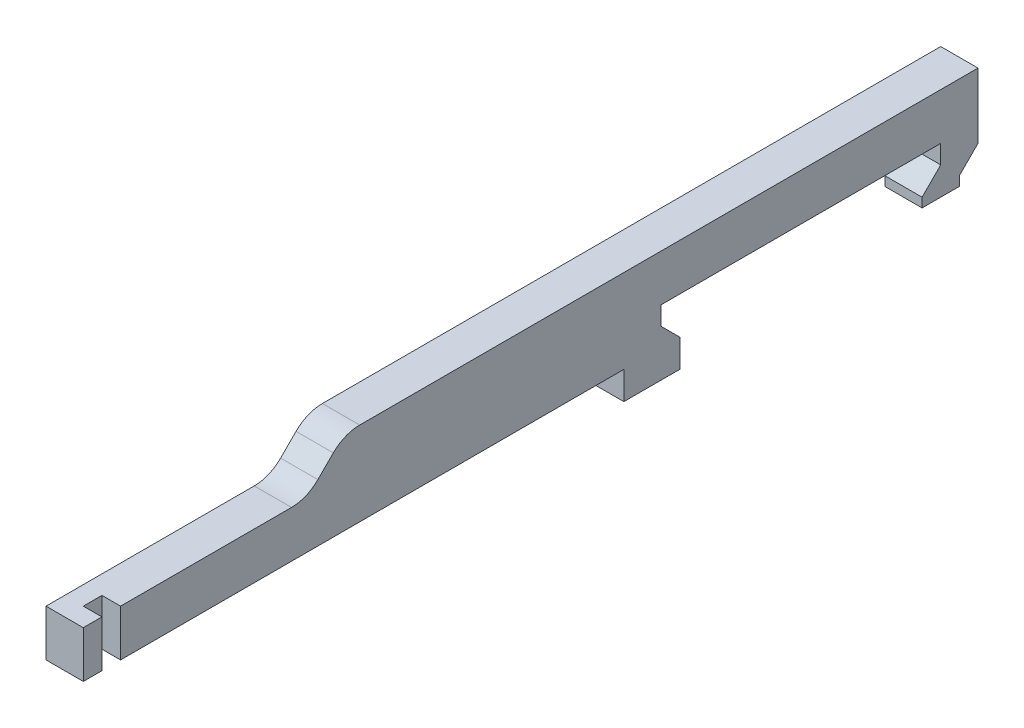
SolidWorks part; units mm, degrees
ref_plane "Спереди" through (0, 0, 0) normal (0, 0, 1) x (1, 0, 0)
ref_plane "Сверху" through (0, 0, 0) normal (0, 1, 0) x (1, 0, 0)
ref_plane "Справа" through (0, 0, 0) normal (1, 0, 0) x (0, 0, -1)
sketch "Эскиз1" plane through (0, 0, 0) normal (1, 0, 0) x (0, 0, -1)
  line L0 (12, 2.5) -> (14, 4.5)
  line L1 (0, 0) -> (12, 0)
  line L2 (0, 0) -> (0, 2.5)
  line L3 (0, 2.5) -> (12, 2.5)
  line L4 (12, 0) -> (12, 2.5)
  line L5 (14, 4.5) -> (14, 2.5) construction
  line L6 (14, 2.5) -> (12, 2.5) construction
  line L7 (14, 4.5) -> (29, 4.5)
  line L8 (12, 0) -> (29, 0)
  line L9 (29, 0) -> (29, -1.5)
  line L10 (29, -1.5) -> (32, -1.5)
  line L11 (32, -1.5) -> (32, 0)
  line L12 (32, 0) -> (31, 1)
  line L13 (31, 1) -> (31, 2)
  line L14 (31, 2) -> (46, 2)
  line L15 (32, 0) -> (31, 0) construction
  line L16 (31, 0) -> (31, 1) construction
  line L17 (38.5, 2) -> (38.5, 1) construction
  line L18 (45, 0) -> (46, 1)
  line L19 (46, 1) -> (46, 2)
  line L20 (45, 0) -> (45, -0.5)
  line L21 (45, -0.5) -> (47, -0.5)
  line L22 (47, -0.5) -> (47, 0)
  line L23 (47, 0) -> (48, 1)
  line L24 (48, 1) -> (48, 4.5)
  line L25 (48, 4.5) -> (29, 4.5)
  dimension "D1" = 2.5
  dimension "D2" = 12
  dimension "D3" = 2
  dimension "D4" = 2
  dimension "D5" = 15
  dimension "D6" = 17
  dimension "D7" = 1.5
  dimension "D8" = 3
  dimension "D9" = 1.5
  dimension "D10" = 1
  dimension "D11" = 1
  dimension "D12" = 1
  dimension "D13" = 15
  dimension "D14" = 0.5
  dimension "D15" = 2
extrude "Бобышка-Вытянуть1" add sketch "Эскиз1" along normal blind 2 contours L24 L25 L7 L0 L4 L8 L9 L10 L11 L12 L13 L14 L19 L18 L20 L21 L22 L23 | L1 L4 L3 L2 region at (0, 1.25, -6) region at (0, 2.3778, -28.5116)
fillet "Скругление1" radius 2 2 edges at (1, 4.5, -14) (1, 2.5, -12)
sketch "Эскиз3" plane through (0, 2.5, 0) normal (0, 1, 0) x (1, 0, 0)
  line L0 (2, 0) -> (2, 1) construction
  line L1 (2, 0) -> (2, 11.1716) construction
  line L2 (2, 1) -> (1, 1)
  line L3 (1, 1) -> (1, 2)
  line L4 (1, 2) -> (2, 2)
  line L5 (2, 2) -> (2, 1)
  dimension "D1" = 1
  dimension "D2" = 1
  dimension "D3" = 1
extrude "Вырез-Вытянуть1" cut sketch "Эскиз3" against normal through all
